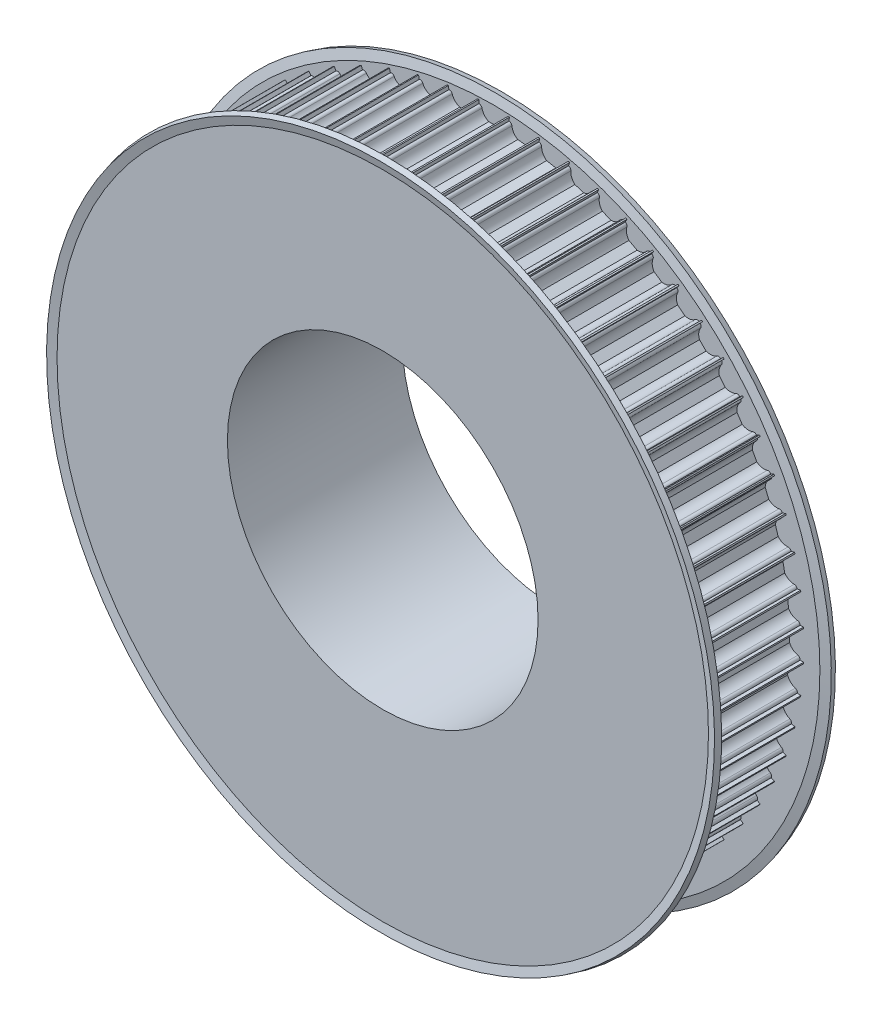
SolidWorks part; units mm, degrees
ref_plane "Front Plane" through (0, 0, 0) normal (0, 0, 1) x (1, 0, 0)
ref_plane "Top Plane" through (0, 0, 0) normal (0, 1, 0) x (1, 0, 0)
ref_plane "Right Plane" through (0, 0, 0) normal (1, 0, 0) x (0, 0, -1)
sketch "Sketch1" plane through (0, 0, 0) normal (1, 0, 0) x (0, 0, -1)
  line L0 (0, 4.4564) -> (24.6246, 4.4564) construction
  line L1 (0, 44.4564) -> (45, 44.4564)
  line L2 (45, 44.4564) -> (45, 59.9564)
  line L3 (45, 59.9564) -> (30, 59.9564)
  line L4 (30, 59.9564) -> (30, 84.4564)
  line L5 (30, 84.4564) -> (0, 84.4564)
  line L6 (0, 84.4564) -> (0, 44.4564)
  dimension "D1" = 80
  dimension "D2" = 30
  dimension "D3" = 15
  dimension "D6" = 15.5
  dimension "D7" = 40
revolve "Revolve1" add sketch "Sketch1" angle 360 about L0
sketch "Sketch2" plane through (0, 0, 0) normal (0, 0, 1) x (1, 0, 0)
  line L0 (0, 84.4564) -> (0, -75.5436) construction
  line L1 (-3.6742, 83.4564) -> (-3.75, 83.4564)
  line L2 (-3.75, 83.4564) -> (-3.75, 85.4564)
  line L3 (-3.75, 85.4564) -> (3.75, 85.4564)
  line L4 (3.75, 85.4564) -> (3.75, 83.4564)
  line L5 (3.75, 83.4564) -> (3.6742, 83.4564)
  line L6 (-1.199, 80.7064) -> (1.199, 80.7064)
  arc A0 (2.9394, 82.8564) -> (1.199, 80.7064) centre (0, 83.4564) cw
  circle A1 centre (0, 4.4564) radius 80 construction
  arc A2 (2.9394, 82.8564) -> (3.6742, 83.4564) centre (3.6742, 82.7064) cw
  arc A3 (-2.9394, 82.8564) -> (-3.6742, 83.4564) centre (-3.6742, 82.7064) ccw
  arc A4 (-1.199, 80.7064) -> (-2.9394, 82.8564) centre (0, 83.4564) cw
  point P9 (0, 4.4564)
  point P15 (0, 85.4564)
  point P18 (3, 83.4564)
  point P21 (-3, 83.4564)
  dimension "D1" = 3
  dimension "D5" = 0.75
  dimension "D2" = 79
  dimension "D3" = 7.5
  dimension "D4" = 2
  dimension "D6" = 2.75
extrude "Cut-Extrude1" cut sketch "Sketch2" against normal up to next
pattern_circular "CirPattern1" count 64 over 360 about axis through (0, 4.4564, 0) along (0, 0, 1) of "Cut-Extrude1"
sketch "Sketch3" plane through (0, 0, 0) normal (1, 0, 0) x (0, 0, -1)
  line L0 (15, -36.5211) -> (15, -13.7216) construction
  line L1 (30, -36.5211) -> (0, -36.5211) construction
  line L2 (30, -13.7216) -> (0, -13.7216) construction
  line L3 (30, 59.9564) -> (30, 84.8689)
  line L4 (30, 84.8689) -> (30.5701, 86.9964)
  line L5 (30.5701, 86.9964) -> (29.1212, 87.3846)
  line L6 (29.1212, 87.3846) -> (28.5, 85.0664)
  line L7 (28.5, 85.0664) -> (28.5, 59.9564)
  line L8 (28.5, 59.9564) -> (30, 59.9564)
  line L9 (45, 59.9564) -> (30, 59.9564) construction
  line L10 (1.5, 85.0664) -> (1.5, 59.9564)
  line L11 (0.8788, 87.3846) -> (1.5, 85.0664)
  line L12 (-0.5701, 86.9964) -> (0.8788, 87.3846)
  line L13 (0, 84.8689) -> (-0.5701, 86.9964)
  line L14 (0, 59.9564) -> (0, 84.8689)
  line L15 (1.5, 59.9564) -> (0, 59.9564)
  line L16 (15, -36.5211) -> (15, 38.502) construction
  line L17 (0, 38.502) -> (30, 38.502) construction
  line L18 (15, 0.9904) -> (-17.187, 0.9904) construction
  dimension "D1" = 15
  dimension "D2" = 1.5
  dimension "D3" = 25.11
  dimension "D4" = 2.4
revolve "Revolve3" add sketch "Sketch3" angle 360 about L18
